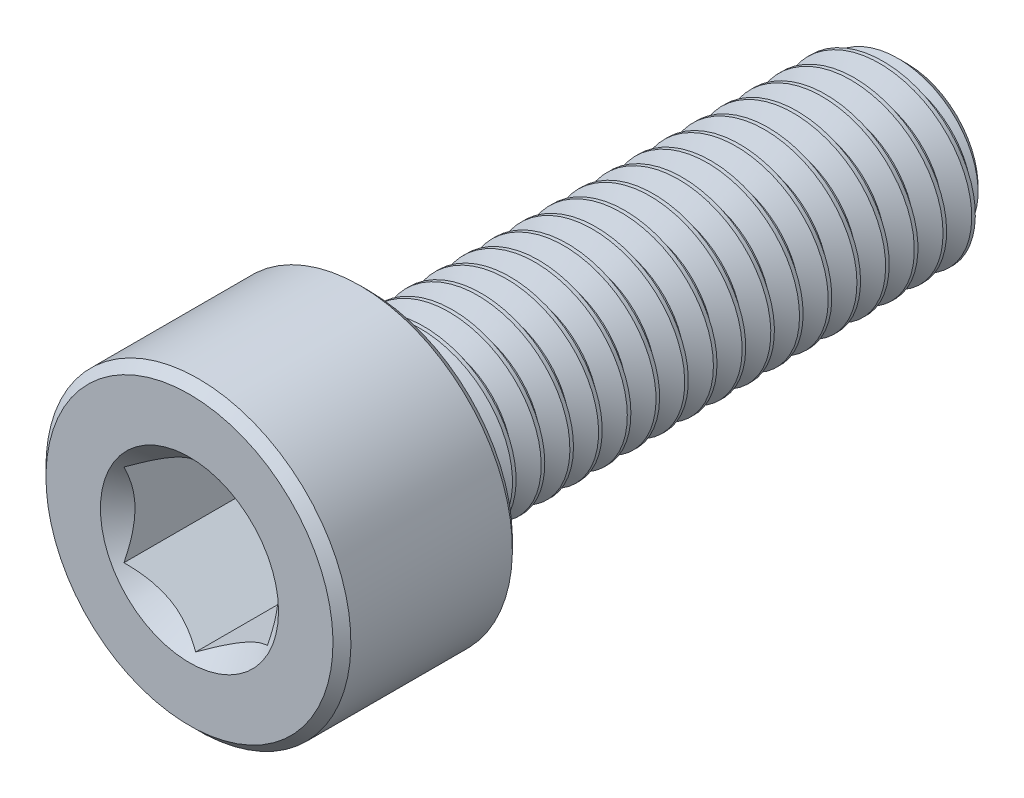
SolidWorks part; units mm, degrees
ref_plane "Front Plane" through (0, 0, 0) normal (0, 0, 1) x (1, 0, 0)
ref_plane "Top Plane" through (0, 0, 0) normal (0, 1, 0) x (1, 0, 0)
ref_plane "Right Plane" through (0, 0, 0) normal (1, 0, 0) x (0, 0, -1)
sketch "Sketch1" plane through (0, 0, 0) normal (1, 0, 0) x (0, 0, -1)
  line L0 (-10, 0) -> (10, 0) construction
  line L1 (10, 0) -> (10, 1.9804) construction
  line L2 (10, 1.9804) -> (9.4804, 2.5) construction
  line L3 (9.4804, 2.5) -> (9.4, 2.5) construction
  line L4 (9.4, 2.5) -> (-5, 2.5) construction
  line L5 (-5, 2.5) -> (-5, 4.25) construction
  line L6 (-5, 4.25) -> (-10, 4.25) construction
  line L7 (-10, 4.25) -> (-10, 0) construction
  line L8 (10, 1.9804) -> (10, 2.5) construction
  line L9 (9.95, 2.5866) -> (10.35, 1.8938) construction
  line L10 (10.35, 1.8938) -> (10.75, 2.5866) construction
  line L11 (10.75, 2.5866) -> (9.95, 2.5866) construction
  line L12 (10.35, 2.5866) -> (10.35, 2.5) construction
  line L13 (10.35, 1.8938) -> (10.35, 1.9804) construction
  line L14 (10.3, 1.9804) -> (10.4, 1.9804) construction
  line L15 (10, 2.5) -> (10.7, 2.5) construction
  line L16 (9.975, 2.5433) -> (10.725, 2.5433) construction
  line L17 (10, 0) -> (10, -2.5) construction
  line L18 (-5.25, 4.25) -> (-5, 4) construction
  line L19 (-9.75, 4.25) -> (-10, 4) construction
  line L20 (-5, 2.5) -> (-5, 0) construction
  line L21 (-5, 1.25) -> (0, 1.25) construction
  line L22 (0, 1.25) -> (5, 1.25) construction
  line L23 (5, 1.25) -> (10, 1.25) construction
  line L24 (0, 1.25) -> (0, 2.5) construction
  line L25 (0, 2.5) -> (0, 4.25) construction
  line L26 (5, 1.25) -> (5, 4.25) construction
  point P0 (-10, 2)
  point P3 (8, 2.5)
  point P4 (0, 0)
  point P18 (5, 2.5)
  point P22 (10.35, 1.9804)
  point P24 (9.4, 2.5)
  point P25 (10.35, 2.5)
  point P28 (10.35, 2.5433)
  point P29 (8, -2.5)
  point P30 (0, 2.5)
  point P31 (-7.5, 4.25)
  point P37 (-5.875, 4.25)
  point P38 (-9.625, 4.25)
  point P45 (0, 1.25)
  point P46 (5, 1.25)
  dimension "D2" = 0.1
  dimension "D7" = 0.25
  dimension "D8" = 0.25
  dimension "D9" = 0.25
  dimension "D10" = 0.125
  dimension "D11" = 0.625
  dimension "Drive Size" = 4
  dimension "Head Diameter" = 8.5
  dimension "Head Height" = 5
  dimension "Thread Pitch" = 0.8
  dimension "Thread Dia" = 5
  dimension "Length" = 15
  dimension "D12" = 0.6
  dimension "D4" = 2
  dimension "D3" = 45
sketch "Sketch2" plane through (0, 0, 0) normal (1, 0, 0) x (0, 0, -1)
  line L0 (-10, 0) -> (-10, 4)
  line L1 (-9.75, 4.25) -> (-5.25, 4.25)
  line L2 (-5, 4) -> (-5, 2.75)
  line L4 (9.4804, 2.5) -> (10, 1.9804)
  line L5 (10, 1.9804) -> (10, 0)
  line L6 (-5, 4.25) -> (-10, 4.25) construction
  line L7 (10, 0) -> (-10, 0)
  line L8 (-9.75, 4.25) -> (-10, 4) construction
  line L10 (-9.75, 4.25) -> (-10, 4)
  line L14 (-5.25, 4.25) -> (-5, 4) construction
  line L16 (-5.25, 4.25) -> (-5, 4)
  line L17 (-5, 2.5) -> (-5, 4.25) construction
  line L19 (-4.75, 2.5) -> (9.4804, 2.5)
  line L20 (9.4, 2.5) -> (-5, 2.5) construction
  arc A1 (-5, 2.75) -> (-4.75, 2.5) centre (-4.75, 2.75) ccw
  dimension "D3" = 0.25
revolve "Revolve1" add sketch "Sketch2" angle 360 about L7
sketch "Sketch3" plane through (0, 0, 10) normal (0, 0, 1) x (1, 0, 0)
  line L1 (2, -1.1547) -> (2, 1.1547)
  line L2 (2, 1.1547) -> (0, 2.3094)
  line L3 (0, 2.3094) -> (-2, 1.1547)
  line L4 (-2, 1.1547) -> (-2, -1.1547)
  line L5 (-2, -1.1547) -> (0, -2.3094)
  line L6 (0, -2.3094) -> (2, -1.1547)
  circle A0 centre (0, 0) radius 2 construction
  circle A1 centre (0, 0) radius 4.25 construction
  circle A2 centre (0, 0) radius 4.25 construction
  circle A3 centre (0, 0) radius 2.3094 construction
  point P13 (0, 0)
  dimension "D1" = 4.6188
extrude "Cut-Extrude1" cut sketch "Sketch3" against normal offset from surface (4 mm away) 1 up to face at (0, 4, 5)
sketch "Sketch4" plane through (0, 0, 10) normal (0, 0, 1) x (1, 0, 0)
  circle A0 centre (0, 0) radius 2.4826
  dimension "D1" = 4.9652
extrude "Cut-Extrude2" cut sketch "Sketch4" against normal up to vertex (2.5 mm away) draft 45 up to point (0, 4.25, 7.5)
sketch "Sketch11" plane through (0, 0, 0) normal (1, 0, 0) x (0, 0, -1)
  line L0 (-10, 0) -> (10, 0) construction
  line L1 (-10, 0) -> (10, 0) construction
  line L2 (-2.1875, 0) -> (-2.1875, 2.5) construction
  line L3 (9.4, 2.5) -> (-5, 2.5) construction
  line L4 (7.1875, 0) -> (7.1875, 2.5) construction
  line L6 (10, 1.9804) -> (10, 2.5) construction
  point P2 (-2.1875, 0)
  point P3 (7.1875, 0)
  dimension "D1" = 2.8125
  dimension "D2" = 2.8125
sketch "Sketch6" plane through (0, 0, -10) normal (0, 0, -1) x (-1, 0, 0)
  circle A0 centre (0, 0) radius 2.5
curve "Helix/Spiral1" pitch 0.8 height 15.8 radius 2.5 centre (0, 0, -10) axis (0, 0, 1) start towards (0, 1, 0)
sketch "Sketch10" plane through (0, 0, 0) normal (1, 0, 0) x (0, 0, -1)
  line L0 (-4.75, -4.25) -> (-4.75, 4.25)
  line L5 (-10, 0) -> (10, 0) construction
  line L6 (-4.75, 2.5) -> (-4.75, -2.5) construction
  point P3 (-4.75, 0)
split "Split1" trim tools "Sketch10" bodies to split 106 resulting bodies 114 115
sketch "Sketch7" plane through (0, 0, 0) normal (1, 0, 0) x (0, 0, -1)
  line L0 (9.975, 2.5433) -> (10.725, 2.5433)
  line L1 (10.725, 2.5433) -> (10.4, 1.9804)
  line L2 (10.4, 1.9804) -> (10.3, 1.9804)
  line L3 (10.3, 1.9804) -> (9.975, 2.5433)
sweep "Cut-Sweep1" cut profiles "Sketch7" path "Helix/Spiral1" align with end faces yes
sketch "Sketch8" plane through (0, 0, 0) normal (1, 0, 0) x (0, 0, -1)
  line L0 (-5, 0) -> (-5, 2.5)
  line L1 (-4.75, -2.5) -> (-4.75, 2.5) construction
  line L2 (-5, 2.5) -> (-4.75, 2.5)
  line L4 (-4.75, 2.5) -> (-3.3066, 0)
  line L5 (-3.3066, 0) -> (-5, 0)
  line L6 (9.4, 2.5) -> (-5, 2.5) construction
  line L7 (-10, 0) -> (10, 0) construction
  dimension "D1" = 60
revolve "Revolve2" add sketch "Sketch8" angle 360 about L5
equation "\"D2@Sketch1\" = \"Thread Pitch@Sketch1\" / 8"
equation "\"D4@Helix/Spiral1\" = \"Thread Pitch@Sketch1\""
equation "\"D7@Sketch1\" = \"Head Height@Sketch1\" * .05"
equation "\"D8@Sketch1\"=\"D7@Sketch1\""
equation "\"D9@Sketch1\"=\"D7@Sketch1\""
equation "\"D10@Sketch1\"=\"D7@Sketch1\"/2"
equation "\"D11@Sketch1\"=\"D10@Sketch1\"*5"
equation "\"D4@Sketch1\"=\"Thread Pitch@Sketch1\"*2.5"
equation "\"D12@Sketch1\"=\"Thread Pitch@Sketch1\"*.75"
equation "\"D3@Helix/Spiral1\"=\"Length@Sketch1\"+\"Thread Pitch@Sketch1\""
equation "\"D3@Sketch2\"=\"Thread Dia@Sketch1\"*0.05"
equation "\"D1@Sketch11\"=\"Length@Sketch1\"*0.1875"
equation "\"D2@Sketch11\"=\"D1@Sketch11\""
equation "\"D1@Sketch4\"=\"D1@Sketch3\"*1.075"
